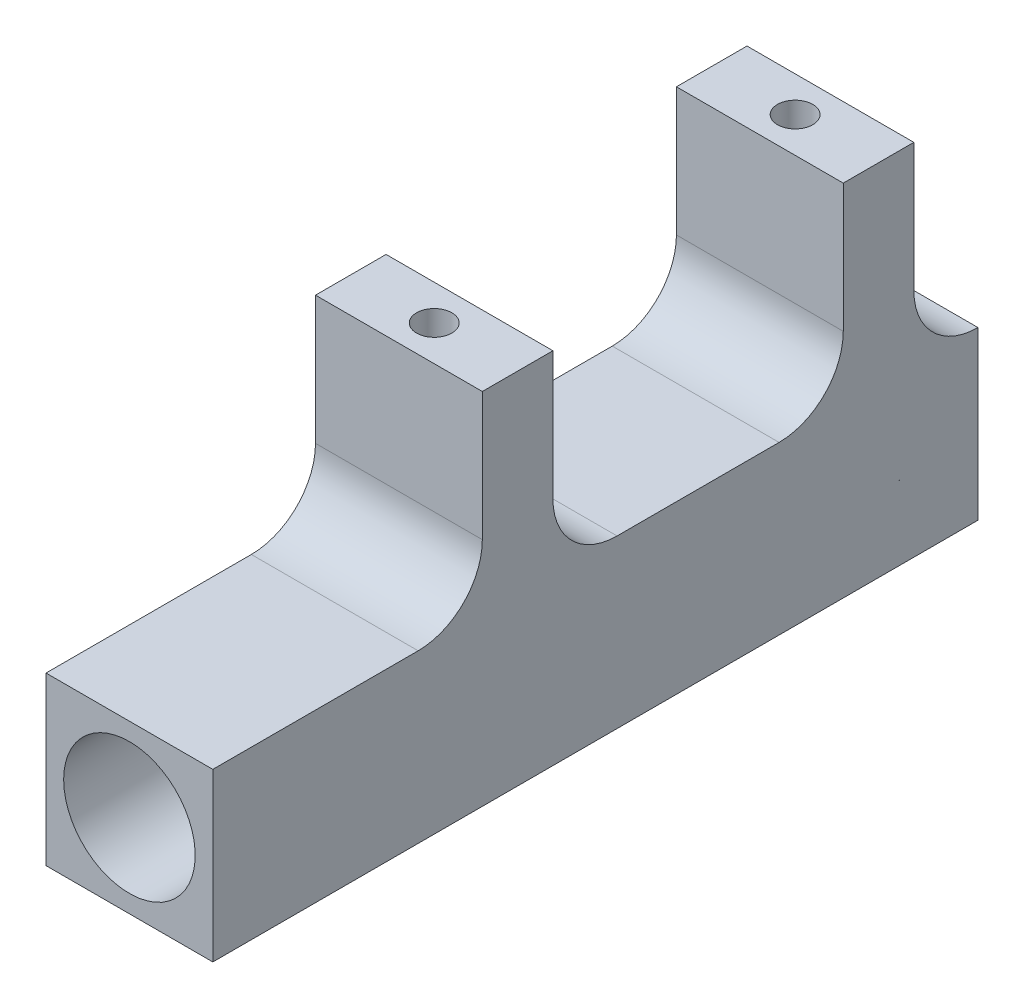
SolidWorks part; units mm, degrees
ref_plane "Front Plane" through (0, 0, 0) normal (0, 0, 1) x (1, 0, 0)
ref_plane "Top Plane" through (0, 0, 0) normal (0, 1, 0) x (1, 0, 0)
ref_plane "Right Plane" through (0, 0, 0) normal (1, 0, 0) x (0, 0, -1)
sketch "Sketch1" plane through (0, 0, 0) normal (0, 0, 1) x (1, 0, 0)
  line L1 (-13, -13) -> (13, -13)
  line L2 (-13, -13) -> (-13, 13)
  line L3 (-13, 13) -> (13, 13)
  line L4 (13, -13) -> (13, 13)
  line L5 (-13, -13) -> (13, 13) construction
  line L6 (-13, 13) -> (13, -13) construction
  circle A0 centre (0, 0) radius 10.25
  dimension "D1" = 13
  dimension "D3" = 20.5
  dimension "D2" = 13
sketch "Sketch2" plane through (0, 0, 0) normal (1, 0, 0) x (0, 0, -1)
  line L0 (0, 13) -> (0, -13) construction
  line L8 (10, 23) -> (10, 43)
  line L10 (21, 23) -> (21, 43)
  line L11 (0, 13) -> (31, 13) construction
  line L12 (10, 43) -> (21, 43)
  line L13 (0, 13) -> (-32, 13)
  line L15 (87.25, -13) -> (-32, -13)
  line L16 (-32, 13) -> (-32, -13)
  line L21 (13, 43) -> (13, 13) construction
  line L22 (18, 43) -> (18, 13) construction
  line L23 (66.25, 23) -> (66.25, 43)
  line L24 (77.25, 23) -> (77.25, 43)
  line L25 (66.25, 43) -> (77.25, 43)
  line L26 (69.25, 43) -> (69.25, 13) construction
  line L27 (74.25, 43) -> (74.25, 13) construction
  line L28 (31, 13) -> (56.25, 13)
  line L29 (87.25, -13) -> (87.25, 13)
  line L30 (56.25, 13) -> (87.25, 13) construction
  arc A0 (0, 13) -> (10, 23) centre (0, 23) ccw
  arc A1 (31, 13) -> (21, 23) centre (31, 23) cw
  arc A2 (56.25, 13) -> (66.25, 23) centre (56.25, 23) ccw
  arc A3 (87.25, 13) -> (77.25, 23) centre (87.25, 23) cw
  point P0 (0, 13)
  point P2 (0, 0)
  point P30 (0, 0)
  point P31 (0, 0)
  point P32 (0, 0)
  point P33 (0, 0)
  dimension "D3" = 10
  dimension "D4" = 10
  dimension "D6" = 5
  dimension "D10" = 10
  dimension "D11" = 10
  dimension "D2" = 30
  dimension "D5" = 11
  dimension "D7" = 26
  dimension "D8" = 3
  dimension "D9" = 45
  dimension "D12" = 11
  dimension "D13" = 30
  dimension "D14" = 5
  dimension "D15" = 3
  dimension "D16" = 101.25
extrude "Boss-Extrude1" add sketch "Sketch2" along normal up to vertex (13 mm away) and the other way up to vertex (13 mm away) contours L28 A1 L10 L12 L8 A0 L13 L16 L15 L29 L30 region at (0, 5.1445, -30.7275) up to point (13, 13, 0) other way up to point (-13, 13, 0)
extrude "Cut-Extrude1" cut sketch "Sketch1" along normal up to surface and the other way up to surface contours A0 up to face at (0, 0, 32) other way up to face at (0, 0, -87.25)
sketch "Sketch3" plane through (0, 43, 0) normal (0, 1, 0) x (1, 0, 0)
  line L0 (-13, 21) -> (13, 10) construction
  line L1 (13, 21) -> (-13, 10) construction
  line L2 (13, 10) -> (-13, 10) construction
  line L3 (-13, 10) -> (-13, 21) construction
  line L4 (13, 21) -> (-13, 21) construction
  line L5 (13, 10) -> (13, 21) construction
  line L6 (-13, 77.25) -> (13, 66.25) construction
  line L7 (13, 77.25) -> (-13, 66.25) construction
  circle A0 centre (0, 15.5) radius 2.75
  circle A1 centre (0, 71.75) radius 2.75
  dimension "D1" = 5.5
  dimension "D2" = 5.5
extrude "Cut-Extrude2" cut sketch "Sketch3" against normal up to surface (32.75 mm away) up to face at (-10.25, 0, 32)
